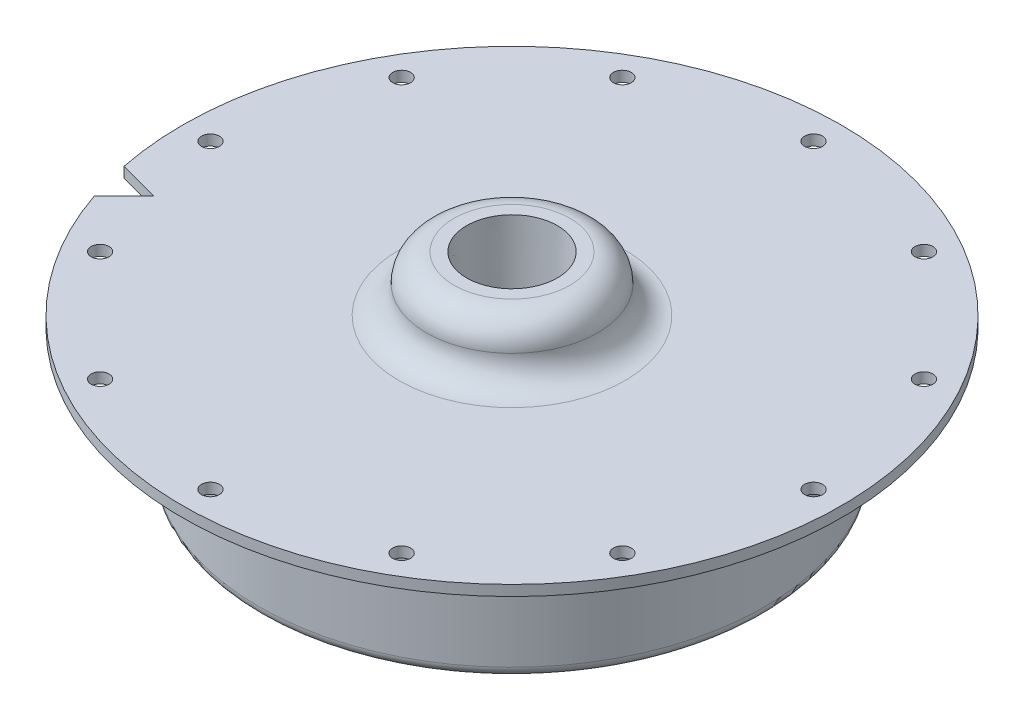
SolidWorks part; units mm, degrees
material "6063-T6"
ref_plane "Front Plane" through (0, 0, 0) normal (0, 0, 1) x (1, 0, 0)
ref_plane "Top Plane" through (0, 0, 0) normal (0, 1, 0) x (1, 0, 0)
ref_plane "Right Plane" through (0, 0, 0) normal (1, 0, 0) x (0, 0, -1)
ref_axis "Axis1" through (0, 55, 0) along (0, -1, 0)
sketch "Sketch1" plane through (0, 0, 0) normal (0, 0, 1) x (1, 0, 0)
  line L0 (-49.784, 0) -> (-39.7637, 0)
  line L1 (0, 55) -> (0, -55) construction
  line L2 (-49.784, 0) -> (-49.784, 1.5875)
  line L3 (-5.588, 9.906) -> (-8.763, 9.906)
  line L5 (-5.588, 9.906) -> (-5.588, 0)
  line L6 (-5.588, 0) -> (0, 0) construction
  line L7 (-49.784, 0) -> (-49.784, 1.5875) construction
  line L8 (-5.588, 1.5875) -> (-5.588, 0) construction
  line L9 (-38.1762, -1.5875) -> (-38.1762, -17.4625)
  line L11 (-35.0012, -17.4625) -> (-35.0012, -3.175)
  line L12 (-31.8262, 0) -> (-5.588, 0)
  line L13 (0, -201000) -> (0, 249000) construction
  line L14 (-49.784, 1.5875) -> (-17.0815, 1.5875)
  arc A0 (-35.0012, -3.175) -> (-31.8262, 0) centre (-31.8262, -3.175) cw
  arc A1 (-38.1762, -1.5875) -> (-39.7637, 0) centre (-39.7637, -1.5875) ccw
  arc A2 (-17.0815, 1.5875) -> (-12.9223, 5.7467) centre (-17.0815, 5.7467) ccw
  arc A3 (-8.763, 9.906) -> (-12.9223, 5.7467) centre (-8.763, 5.7467) ccw
  arc A4 (-38.1762, -17.4625) -> (-35.0012, -17.4625) centre (-36.5887, -17.4625) ccw
  point P18 (-35.0012, 0)
  dimension "D4" = 3.175
  dimension "D5" = 1.5875
  dimension "D1" = 3.175
  dimension "D2" = 38.1762
  dimension "D3" = 17.4625
  dimension "D6" = 1.5875
  dimension "D7" = 3.175
  dimension "D8" = 9.906
revolve "Revolve1" add sketch "Sketch1" angle 360 about axis through (0, 55, 0) along (0, -1, 0)
ref_plane "Hole Location Plane" through (0, 3.175, 0) normal (0, 1, 0) x (1, 0, 0)
sketch "Hole Location" plane through (0, 3.175, 0) normal (0, 1, 0) x (1, 0, 0)
  line L0 (0, 0) -> (-45.5549, 0) construction
  circle A0 centre (0, 0) radius 45.5549 construction
  dimension "D1" = 91.1098
hole_wizard "#36 (0.1065) Diameter Hole1" positions "Sketch2" profile "Sketch3" hole size "#36" standard "ANSI Inch" end condition through all
sketch "Sketch2" plane through (0, 1.5875, 0) normal (0, 1, 0) x (1, 0, 0)
  point P0 (-45.5549, 0)
sketch "Sketch3" plane through (-45.5549, 1.5875, 0) normal (1, 0, 0) x (0, 0, 1)
  line L0 (0, 0) -> (0, 20.6375)
  line L1 (0, 20.6375) -> (1.3525, 20.6375)
  line L2 (1.3525, 20.6375) -> (1.3525, 0)
  line L5 (1.3525, 0) -> (0, 0)
  line L11 (0, -6.35) -> (0, 107.95) construction
  dimension "Thru Hole Dia." = 2.7051
  dimension "Thru Hole Depth" = 20.6375
pattern_circular "CirPattern1" count 12 over 360 of "#36 (0.1065) Diameter Hole1"
hole_wizard "1/4 NPT Tapped Hole1" positions "Sketch4" profile "Sketch5" size "1/4" standard "ANSI Inch" end condition through all
sketch "Sketch4" plane through (0, 9.906, 0) normal (0, 1, 0) x (1, 0, 0)
  point P0 (0, 0)
sketch "Sketch5" plane through (0, 9.906, 0) normal (1, 0, 0) x (0, 0, 1)
  line L0 (0, 0) -> (0, 28.956)
  line L1 (0, 28.956) -> (5.5626, 28.956)
  line L2 (-6.558, 9.906) -> (-6.8546, 0) construction
  line L3 (5.5626, 28.956) -> (5.5626, 9.906)
  line L4 (5.5626, 9.906) -> (6.558, 9.906)
  line L5 (6.558, 9.906) -> (6.8546, 0)
  line L7 (6.8546, 0) -> (0, 0)
  line L8 (0, -6.35) -> (0, 107.95) construction
  line L11 (-5.5626, 9.906) -> (-6.558, 9.906) construction
  dimension "Thru Tap Drill Dia." = 11.1252
  dimension "Thru Tap Drill Depth" = 28.956
  dimension "Thread Dia." = 13.7092
  dimension "Thread Angle" = 3.43
  dimension "Thread Depth" = 9.906
sketch "Sketch6" plane through (0, 1.5875, 0) normal (0, 1, 0) x (1, 0, 0)
  line L0 (0, 0) -> (-48.0877, -12.885) construction
  line L1 (0, 0) -> (-45.5549, 0) construction
  line L2 (-47.168, -15.9256) -> (-42.6779, -11.4355)
  line L3 (-42.6779, -11.4355) -> (-48.8115, -9.792)
  circle A0 centre (0, 0) radius 49.784 construction
  arc A1 (-47.168, -15.9256) -> (-48.8115, -9.792) centre (0, 0) cw
  circle M16 centre (0, 0) radius 49.784
  dimension "D1" = 15
  dimension "D2" = 60
  dimension "D3" = 6.35
extrude "Cut-Extrude1" cut sketch "Sketch6" against normal up to surface (1.5875 mm away) contours L2 L0 A1 | L0 L3 M16 region at (-45.9878, 1.5875, 13.4214) region at (-46.5373, 1.5875, 11.3707) up to face at (-39.4517, 0, -24.13)
equation "\"D1@Hole Location\"=\"TANK DIAMETER@Cryo Tank.Assembly\"+\"GASKET SEAT THICKNESS@Cryo Tank.Assembly\"+\"LINER THICKNESS@Cryo Tank.Assembly\"+\"SHRINK FIT DELTA@Cryo Tank.Assembly\""
equation "\"D2@Sketch1\"=\"TANK DIAMETER@Cryo Tank.Assembly\"/2+0.003"
equation "\"D3@Sketch1\"=0.5+0.125+0.0625"
